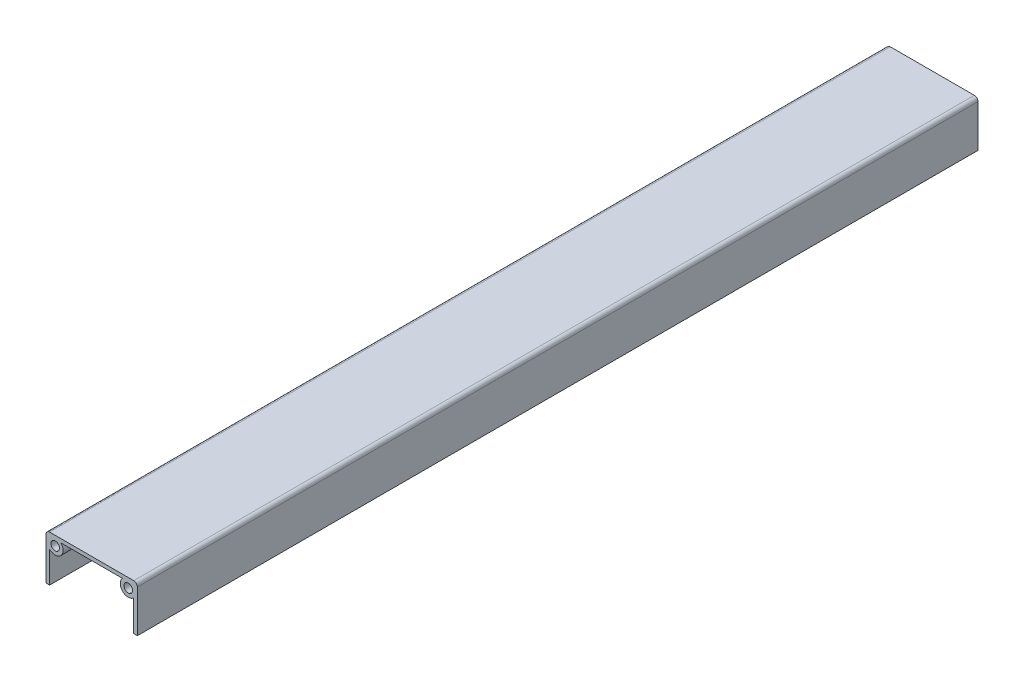
SolidWorks part; units mm, degrees
ref_plane "Front Plane" through (0, 0, 0) normal (0, 0, 1) x (1, 0, 0)
ref_plane "Top Plane" through (0, 0, 0) normal (0, 1, 0) x (1, 0, 0)
ref_plane "Right Plane" through (0, 0, 0) normal (1, 0, 0) x (0, 0, -1)
sketch "Sketch1" plane through (0, 0, 0) normal (0, 0, 1) x (1, 0, 0)
  line L0 (0, 31.75) -> (0, -31.75) construction
  line L1 (-31.75, -31.75) -> (31.75, -31.75)
  line L2 (-31.75, -31.75) -> (-31.75, 31.75)
  line L3 (-31.75, 31.75) -> (31.75, 31.75)
  line L4 (31.75, -31.75) -> (31.75, 31.75)
  line L5 (-31.75, -31.75) -> (31.75, 31.75) construction
  line L6 (-31.75, 31.75) -> (31.75, -31.75) construction
  line L7 (-31.75, 0) -> (31.75, 0) construction
  circle A0 centre (-25.4, 25.4) radius 3
  circle A1 centre (25.4, -25.4) radius 3
  circle A2 centre (-25.4, -25.4) radius 3
  circle A3 centre (25.4, 25.4) radius 3
  point P0 (0, 0)
  dimension "D3" = 6
  dimension "D9" = 50.8
  dimension "D4" = 50.8
  dimension "D1" = 63.5
  dimension "D2" = 63.5
  dimension "D5" = 6.35
extrude "Boss-Extrude1" add sketch "Sketch1" along normal mid plane 584.2
fillet "Fillet1" radius 2.54 4 edges at (-31.75, -31.75, 0) (31.75, -31.75, 0) (-31.75, 31.75, 0) (31.75, 31.75, 0)
shell "Shell1" thickness 2.54 removed face at (-28.4, -25.4, -292.1) removed face at (0, 0, 292.1)
sketch "Sketch3" plane through (0, 0, 292.1) normal (0, 0, 1) x (1, 0, 0)
  line L1 (-31.75, 29.21) -> (-31.75, -29.21) construction
  line L2 (-31.75, -0.1289) -> (31.9153, -0.1289)
  line L3 (-31.75, -0.1289) -> (-31.75, -31.8789)
  line L4 (-31.75, -31.8789) -> (31.9153, -31.8789)
  line L5 (31.9153, -0.1289) -> (31.9153, -31.8789)
  dimension "D1" = 31.75
extrude "Cut-Extrude2" cut sketch "Sketch3" against normal through all
equation "\"D1@Boss-Extrude1\"=\"robotwidth@2016 Chassis 3.0.Assembly\"-6in"
